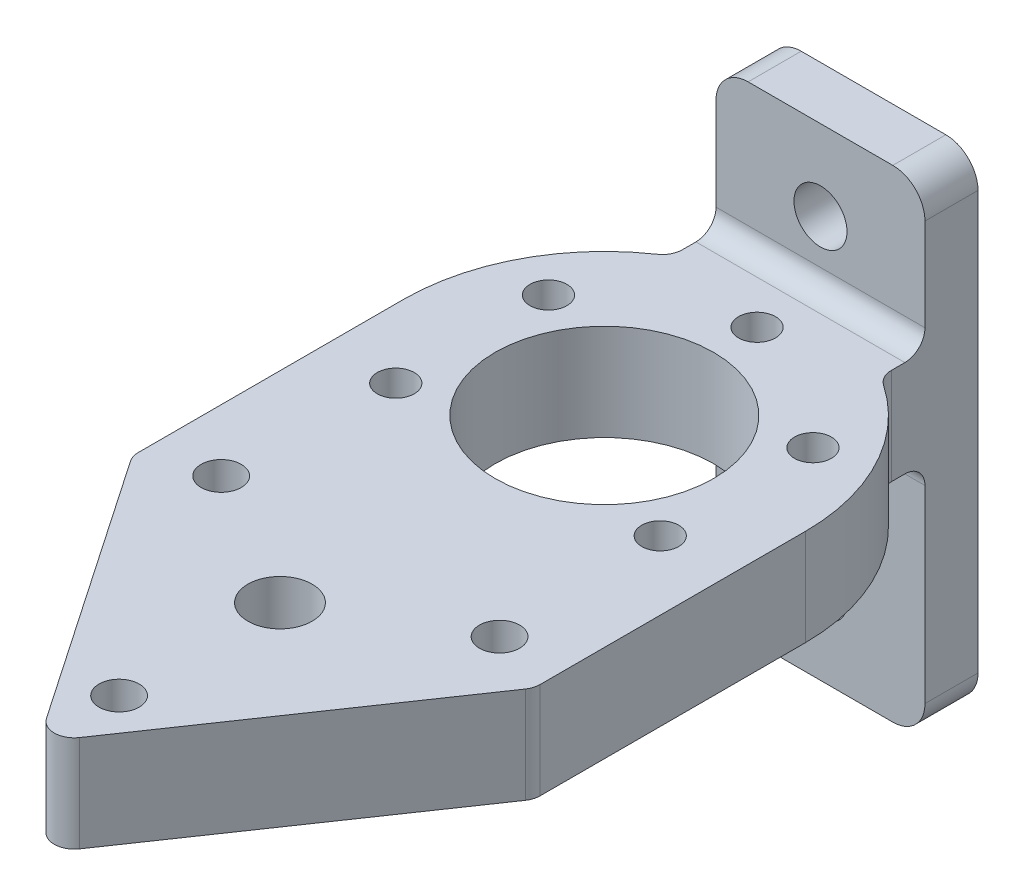
SolidWorks part; units mm, degrees
material "PLA"
ref_plane "Plan de face" through (0, 0, 0) normal (0, 0, 1) x (1, 0, 0)
ref_plane "Plan de dessus" through (0, 0, 0) normal (0, 1, 0) x (1, 0, 0)
ref_plane "Plan de droite" through (0, 0, 0) normal (1, 0, 0) x (0, 0, -1)
sketch "Esquisse1" plane through (0, 0, 0) normal (0, 0, 1) x (1, 0, 0)
  line L0 (55, 0) -> (-55, 0) construction
  line L1 (-6.5, -15) -> (6.5, -15)
  line L2 (-6.5, -15) -> (-6.5, 15)
  line L3 (-6.5, 15) -> (6.5, 15)
  line L4 (6.5, -15) -> (6.5, 15)
  line L5 (-6.5, -15) -> (6.5, 15) construction
  line L6 (-6.5, 15) -> (6.5, -15) construction
  circle A0 centre (0, 10) radius 1.65
  circle A1 centre (0, -10) radius 1.65
  point P0 (0, 0)
  dimension "D4" = 3.3
  dimension "D1" = 30
  dimension "D2" = 13
  dimension "D3" = 10
extrude "Boss.-Extru.1" add sketch "Esquisse1" along normal blind 3.3
fillet "Congé1" radius 2 4 edges at (6.5, -15, 1.65) (-6.5, -15, 1.65) (6.5, 15, 1.65) (-6.5, 15, 1.65)
sketch "Esquisse2" plane through (0, 0, 3.3) normal (0, 0, 1) x (1, 0, 0)
  line L0 (6.5, -13) -> (6.5, 13) construction
  line L3 (-6.5, 6) -> (6.5, 6)
  line L5 (-6.5, 13) -> (-6.5, -13) construction
  line L7 (-6.5, 6) -> (-6.5, 0)
  line L10 (-6.5, 0) -> (6.5, 0)
  line L14 (6.5, 6) -> (6.5, 0)
  point P0 (0, 0)
  point P8 (0, 0)
  dimension "D1" = 0
  dimension "D3" = 6
extrude "Boss.-Extru.2" add sketch "Esquisse2" along normal blind 2.77
sketch "Esquisse4" plane through (0, 6, 0) normal (0, 1, 0) x (1, 0, 0)
  line L1 (-6.5, -6.07) -> (6.5, -6.07)
  line L3 (-6.5, -27.4242) -> (6.5, -27.4242)
  circle A4 centre (0, -16.7471) radius 6.8
  arc A5 (-6.5, -6.07) -> (-6.5, -27.4242) centre (0, -16.7471) ccw
  arc A6 (6.5, -27.4242) -> (6.5, -6.07) centre (0, -16.7471) ccw
  point P25 (0, -16.7471)
  point P28 (0, -16.7471)
  dimension "D2" = 12.5
  dimension "D3" = 13
  dimension "D6" = 13.6
  dimension "D1" = 12.5
extrude "Boss.-Extru.4" add sketch "Esquisse4" against normal up to surface (6 mm away) up to face at (0, 0, 4.685)
sketch "Esquisse6" plane through (0, 6, 0) normal (0, 1, 0) x (1, 0, 0)
  line L2 (0, -16.7471) -> (8.2272, -11.9971) construction
  line L3 (0, -16.7471) -> (-8.2272, -11.9971) construction
  line L4 (0, -16.7471) -> (0, -7.2471) construction
  line L5 (0, -16.7471) -> (-8.2272, -21.4971) construction
  line L6 (0, -16.7471) -> (0, -26.2471) construction
  line L7 (0, -16.7471) -> (8.2272, -21.4971) construction
  circle A0 centre (0, -7.2471) radius 1.15
  circle A1 centre (-8.2272, -11.9971) radius 1.15
  circle A2 centre (8.2272, -11.9971) radius 1.15
  circle A3 centre (-8.2272, -21.4971) radius 1.15
  circle A7 centre (8.2272, -21.4971) radius 1.15
  dimension "D2" = 2.3
  dimension "D5" = 2.3
  dimension "D6" = 2.3
  dimension "D7" = 9.5
  dimension "D14" = 2.3
  dimension "D15" = 2.3
  dimension "D1" = 9.5
  dimension "D3" = 60
  dimension "D4" = 60
  dimension "D8" = 9.5
  dimension "D9" = 60
  dimension "D10" = 60
  dimension "D11" = 9.5
  dimension "D12" = 9.5
  dimension "D13" = 9.5
extrude "Enlèv. mat.-Extru.2" cut sketch "Esquisse6" against normal through all
sketch "Esquisse8" plane through (0, 6, 0) normal (0, 1, 0) x (1, 0, 0)
  line L6 (-6.5, -27.4242) -> (6.5, -27.4242) construction
  line L8 (0, -9.9471) -> (0, -23.5471) construction
  line L9 (0, -36.9271) -> (0, -27.4242) construction
  line L10 (0, -36.9271) -> (8.6603, -31.9271) construction
  line L11 (0, -36.9271) -> (-8.6603, -31.9271) construction
  line L16 (12.5, -16.7471) -> (12.5, -33.6271) construction
  line L17 (-12.5, -16.7471) -> (-12.5, -33.6258) construction
  line L18 (0, -51.9371) -> (-12.5, -33.6258)
  line L19 (-12.5, -33.6258) -> (-12.5, -16.7471)
  line L20 (0, -51.9371) -> (12.5, -33.6271)
  line L21 (12.5, -33.6271) -> (12.5, -16.7471)
  line L22 (-6.5, -27.4242) -> (6.5, -27.4242)
  circle A0 centre (0, -36.9271) radius 2
  circle A1 centre (0, -36.9271) radius 10 construction
  circle A2 centre (8.6603, -31.9271) radius 1.25
  circle A3 centre (0, -16.7471) radius 6.8 construction
  circle A4 centre (-8.6603, -31.9271) radius 1.25
  circle A7 centre (0, -46.9371) radius 1.25
  arc A8 (6.5, -27.4242) -> (6.5, -6.07) centre (0, -16.7471) ccw construction
  arc A9 (-6.5, -6.07) -> (-6.5, -27.4242) centre (0, -16.7471) ccw construction
  arc A11 (-12.5, -16.7471) -> (-6.5, -27.4242) centre (0, -16.7471) ccw
  arc A12 (12.5, -16.7471) -> (6.5, -27.4242) centre (0, -16.7471) cw
  point P16 (0, -16.7471)
  dimension "D2" = 4
  dimension "D5" = 2.5
  dimension "D6" = 2.5
  dimension "D7" = 2.5
  dimension "D12" = 10.01
  dimension "D1" = 20.18
  dimension "D3" = 120
  dimension "D4" = 60
  dimension "D8" = 16.8787
  dimension "D9" = 16.88
  dimension "D10" = 5
  dimension "D11" = 8.6603
extrude "Boss.-Extru.5" add sketch "Esquisse8" against normal up to surface (6 mm away) up to face at (0, 0, 8.3971)
fillet "Congé2" radius 1.25 7 edges at (12.5, 3, 33.6271) (-12.5, 3, 33.6258) (0, 3, 51.9371) (0, 0, 3.3) (0, 6, 3.3) (6.5, 3, 6.07) (-6.5, 3, 6.07)
